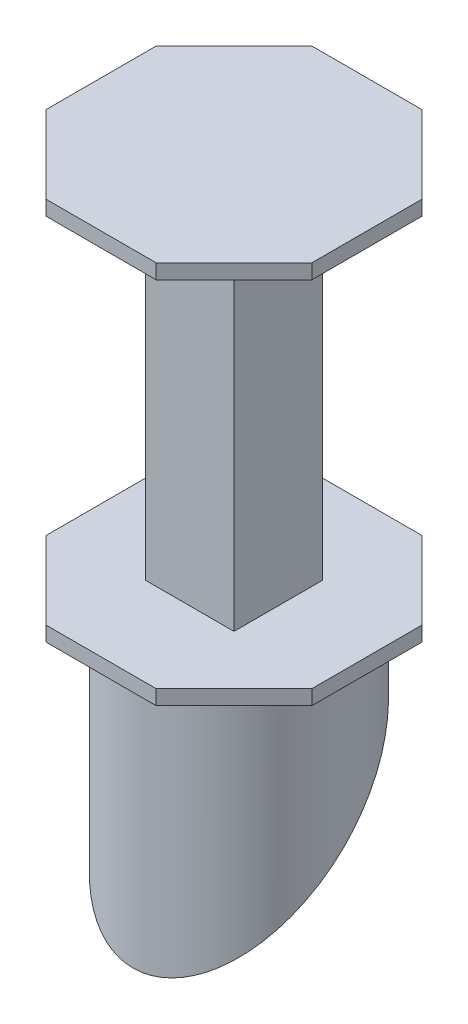
SolidWorks part; units mm, degrees
ref_plane "Front Plane" through (0, 0, 0) normal (0, 0, 1) x (1, 0, 0)
ref_plane "Top Plane" through (0, 0, 0) normal (0, 1, 0) x (1, 0, 0)
ref_plane "Right Plane" through (0, 0, 0) normal (1, 0, 0) x (0, 0, -1)
sketch "Sketch2" plane through (0, 0, 0) normal (1, 0, 0) x (0, 0, -1)
  line L0 (1.0414, 1031.6391) -> (1.0414, 973.3996) construction
  line L1 (1.0414, 1031.6391) -> (-21.7283, 1031.6391)
  line L2 (-21.7283, 1031.6391) -> (-21.7283, 973.3996)
  line L3 (-21.7283, 973.3996) -> (1.0414, 973.3996)
  line L4 (1.0414, 1031.6391) -> (1.0414, 973.3996)
revolve "Revolve1" add sketch "Sketch2" angle 360 about L0
sketch "Sketch3" plane through (0, 0, 0) normal (1, 0, 0) x (0, 0, -1)
  line L0 (-21.7283, 973.3996) -> (23.8111, 1018.9391)
  line L1 (23.8111, 1018.9391) -> (23.8111, 973.3996)
  line L2 (23.8111, 973.3996) -> (-21.7283, 973.3996)
extrude "Cut-Extrude1" cut sketch "Sketch3" against normal through all both and the other way through all
shell "Shell1" thickness 3.175 removed face at (0, 1018.9391, -23.8111)
sketch "Sketch4" plane through (0, 1031.6391, 0) normal (0, 1, 0) x (1, 0, 0)
  line L4 (28.575, 11.8362) -> (11.8362, 28.575)
  line L5 (11.8362, 28.575) -> (-11.8362, 28.575)
  line L6 (-11.8362, 28.575) -> (-28.575, 11.8362)
  line L7 (-28.575, 11.8362) -> (-28.575, -11.8362)
  line L8 (-28.575, -11.8362) -> (-11.8362, -28.575)
  line L9 (-11.8362, -28.575) -> (11.8362, -28.575)
  line L10 (11.8362, -28.575) -> (28.575, -11.8362)
  line L11 (28.575, -11.8362) -> (28.575, 11.8362)
  circle A0 centre (0, 0) radius 28.575 construction
  dimension "D1" = 57.15
extrude "Boss-Extrude1" add sketch "Sketch4" along normal blind 3.175
sketch "Sketch5" plane through (0, 1034.8141, 0) normal (0, 1, 0) x (1, 0, 0)
  line L1 (9.525, 9.525) -> (-9.525, 9.525)
  line L2 (9.525, 9.525) -> (9.525, -9.525)
  line L3 (9.525, -9.525) -> (-9.525, -9.525)
  line L4 (-9.525, 9.525) -> (-9.525, -9.525)
  line L5 (0, -9.525) -> (0, 9.525) construction
  line L6 (9.525, 0) -> (-9.525, 0) construction
  point P0 (0, 0)
  dimension "D1" = 19.05
extrude "Boss-Extrude2" add sketch "Sketch5" along normal blind 76.2
sketch "Sketch6" plane through (0, 1111.0141, 0) normal (0, 1, 0) x (1, 0, 0)
  line L0 (-11.8362, 28.575) -> (-28.575, 11.8362) construction
  line L1 (-28.575, -11.8362) -> (-11.8362, -28.575)
  line L2 (-11.8362, -28.575) -> (11.8362, -28.575)
  line L3 (11.8362, -28.575) -> (28.575, -11.8362)
  line L4 (28.575, -11.8362) -> (28.575, 11.8362)
  line L5 (28.575, 11.8362) -> (11.8362, 28.575)
  line L6 (11.8362, 28.575) -> (-11.8362, 28.575)
  line L7 (-11.8362, 28.575) -> (-28.575, 11.8362)
  line L8 (-28.575, 11.8362) -> (-28.575, -11.8362)
  circle A0 centre (0, 0) radius 28.575 construction
extrude "Boss-Extrude3" add sketch "Sketch6" along normal blind 3.175
